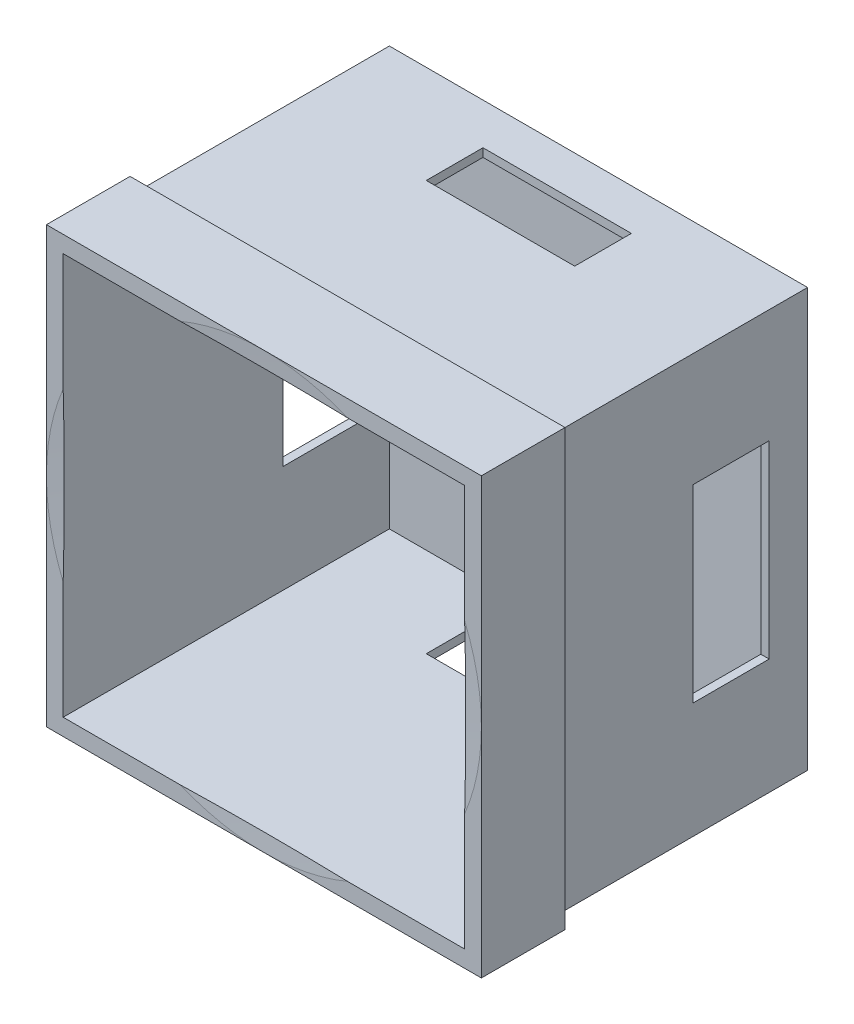
SolidWorks part; units mm, degrees
material "Nylon 101"
ref_plane "Front Plane" through (0, 0, 0) normal (0, 0, 1) x (1, 0, 0)
ref_plane "Top Plane" through (0, 0, 0) normal (0, 1, 0) x (1, 0, 0)
ref_plane "Right Plane" through (0, 0, 0) normal (1, 0, 0) x (0, 0, -1)
sketch "Sketch1" plane through (0, 0, 0) normal (0, 1, 0) x (1, 0, 0)
  line L3 (-127, 76.2) -> (0, 76.2)
  line L4 (-127, 76.2) -> (-127, 0)
  line L5 (-127, 0) -> (0, 0)
  line L6 (0, 76.2) -> (0, 0)
  dimension "D1" = 76.2
  dimension "D2" = 127
extrude "Boss-Extrude1" add sketch "Sketch1" along normal blind 127
shell "Shell1" thickness 2.54 removed face at (-63.5, 63.5, 0)
sketch "Sketch2" plane through (0, 0, 0) normal (0, 0, 1) x (1, 0, 0)
  line L5 (-2.54, 124.46) -> (-2.54, 2.54) construction
  line L6 (-2.54, 124.46) -> (-2.54, 2.54)
  line L7 (-124.46, 124.46) -> (-2.54, 124.46) construction
  line L8 (-124.46, 124.46) -> (-124.46, 2.54) construction
  line L9 (-129.54, -2.54) -> (2.54, -2.54)
  line L10 (2.54, -2.54) -> (2.54, 129.54)
  line L11 (2.54, 129.54) -> (-129.54, 129.54)
  line L12 (-129.54, 129.54) -> (-129.54, -2.54)
  line L13 (-129.54, -2.54) -> (2.54, -2.54)
  line L14 (2.54, -2.54) -> (2.54, 129.54)
  line L15 (2.54, 129.54) -> (-129.54, 129.54)
  line L16 (-129.54, 129.54) -> (-129.54, -2.54)
  line L17 (-124.46, 2.54) -> (-2.54, 2.54) construction
  line L18 (-124.46, 124.46) -> (-2.54, 124.46)
  line L19 (-124.46, 124.46) -> (-124.46, 2.54)
  line L20 (-124.46, 2.54) -> (-2.54, 2.54)
  line M5 (-127, 0) -> (0, 0)
  line M6 (0, 0) -> (0, 127)
  line M7 (0, 127) -> (-127, 127)
  line M8 (-127, 127) -> (-127, 0)
  line M9 (-2.54, 2.54) -> (-124.46, 2.54)
  line M10 (-124.46, 2.54) -> (-124.46, 124.46)
  line M11 (-124.46, 124.46) -> (-2.54, 124.46)
  line M12 (-2.54, 124.46) -> (-2.54, 2.54)
  dimension "D1" = 2.54
extrude "Boss-Extrude2" add sketch "Sketch2" along normal blind 25.4 contours M8 M5 M6 M7 M12 M9 M10 M11 | L15 L16 L13 L14 M5 M8 M7 M6 region at (-127.6721, 63.5, 0) region at (-125.2039, 63.5, 0)
ref_plane "Plane1" through (-63.5, 0, 0) normal (1, 0, 0) x (0, 0, -1)
sketch "Sketch3" plane through (-63.5, 0, 0) normal (-1, 0, 0) x (0, 0, 1)
  line L0 (25.4, 129.54) -> (25.4, -2.54) construction
  line L1 (2004.3962, 63.5) -> (23.1962, 63.5) construction
  circle A0 centre (1013.7962, 63.5) radius 990.6
  point P6 (25.4, 63.5)
  dimension "D1" = 1981.2
revolve "Cut-Revolve2" cut sketch "Sketch3" angle 360 about L1 region at (-63.5, -356.9237, 1013.7962)
sketch "Sketch4" plane through (0, 0, -76.2) normal (0, 0, -1) x (-1, 0, 0)
  line L0 (0, 127) -> (127, 0) construction
  line L1 (127, 0) -> (127, 127) construction
  line L2 (127, 127) -> (0, 0) construction
  line L3 (0, 0) -> (127, 0) construction
  point P4 (63.5, 63.5)
ref_axis "Axis1" through (-63.5, 63.5, -76.2) along (0, 0, 1)
sketch "Sketch5" plane through (-127, 0, 0) normal (-1, 0, 0) x (0, 0, 1)
  line L1 (-41.3415, 92.522) -> (-64.5391, 92.522)
  line L2 (-41.3415, 92.522) -> (-41.3415, 35.0999)
  line L3 (-41.3415, 35.0999) -> (-64.5391, 35.0999)
  line L4 (-64.5391, 92.522) -> (-64.5391, 35.0999)
extrude "Cut-Extrude1" cut sketch "Sketch5" against normal through all
sketch "Sketch6" plane through (0, 0, 0) normal (0, -1, 0) x (1, 0, 0)
  line L1 (-86.0322, -46.4433) -> (-40.9678, -46.4433)
  line L2 (-86.0322, -46.4433) -> (-86.0322, -63.6587)
  line L3 (-86.0322, -63.6587) -> (-40.9678, -63.6587)
  line L4 (-40.9678, -46.4433) -> (-40.9678, -63.6587)
  point P4 (-63.5, -63.6587)
extrude "Cut-Extrude2" cut sketch "Sketch6" against normal through all
